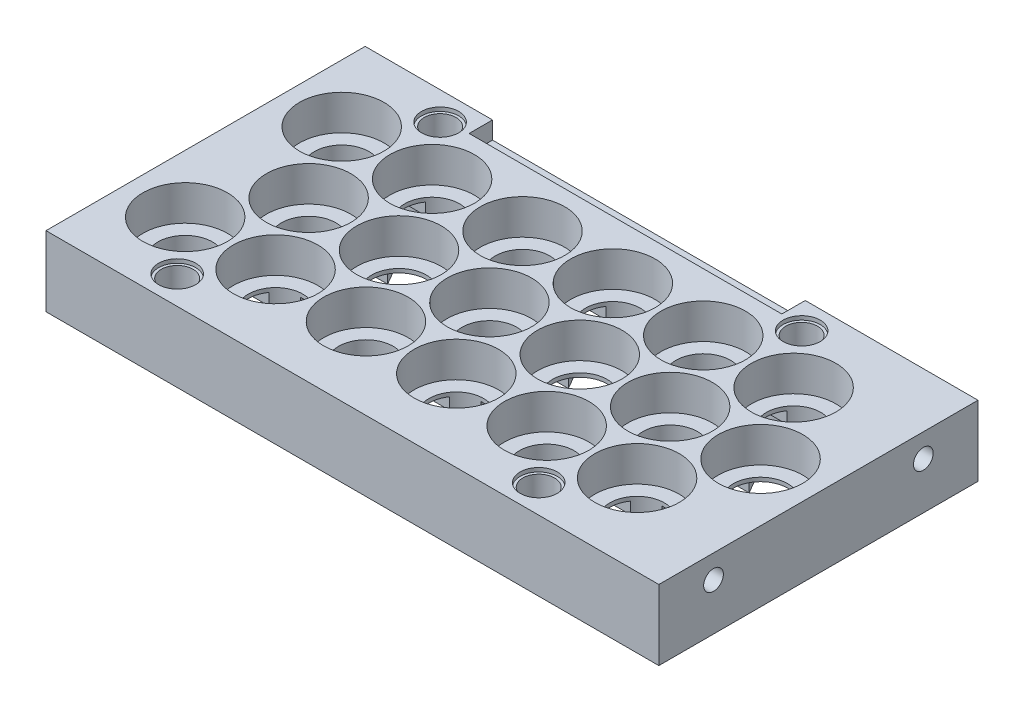
SolidWorks part; units mm, degrees
ref_plane "Front Plane" through (0, 0, 0) normal (0, 0, 1) x (1, 0, 0)
ref_plane "Top Plane" through (0, 0, 0) normal (0, 1, 0) x (1, 0, 0)
ref_plane "Right Plane" through (0, 0, 0) normal (1, 0, 0) x (0, 0, -1)
sketch "Sketch1" plane through (0, 0, 0) normal (0, 1, 0) x (1, 0, 0)
  line L0 (0, 0) -> (11.575, -20.0485) construction
  line L1 (11.575, -20.0485) -> (0, -40.097) construction
  line L2 (0, 0) -> (11.575, 0) construction
  line L3 (11.575, 0) -> (11.575, -20.0485) construction
  line L4 (11.575, -20.0485) -> (11.575, -40.097) construction
  line L5 (11.575, -40.097) -> (0, -40.097) construction
  line L6 (0, 0) -> (23.15, 0) construction
  line L7 (0, 0) -> (23.15, 0) construction
  line L8 (-14.825, -60.922) -> (142.15, -60.922)
  line L9 (-14.825, -60.922) -> (-14.825, 20.825)
  line L10 (-14.825, 20.825) -> (142.15, 20.825)
  line L11 (142.15, -60.922) -> (142.15, 20.825)
  circle A0 centre (0, 0) radius 10.825
  circle A1 centre (11.575, -20.0485) radius 10.825
  circle A2 centre (0, -40.097) radius 10.825
  circle A3 centre (23.15, 0) radius 10.825
  circle A4 centre (34.725, -20.0485) radius 10.825
  circle A5 centre (23.15, -40.097) radius 10.825
  circle A6 centre (46.3, 0) radius 10.825
  circle A7 centre (57.875, -20.0485) radius 10.825
  circle A8 centre (46.3, -40.097) radius 10.825
  circle A9 centre (69.45, 0) radius 10.825
  circle A10 centre (81.025, -20.0485) radius 10.825
  circle A11 centre (69.45, -40.097) radius 10.825
  circle A12 centre (92.6, 0) radius 10.825
  circle A13 centre (104.175, -20.0485) radius 10.825
  circle A14 centre (92.6, -40.097) radius 10.825
  circle A15 centre (115.75, 0) radius 10.825
  circle A16 centre (127.325, -20.0485) radius 10.825
  circle A17 centre (115.75, -40.097) radius 10.825
  circle A18 centre (0, 0) radius 7
  circle A19 centre (11.575, -20.0485) radius 7
  circle A20 centre (0, -40.097) radius 7
  circle A21 centre (23.15, 0) radius 7
  circle A22 centre (34.725, -20.0485) radius 7
  circle A23 centre (23.15, -40.097) radius 7
  circle A24 centre (46.3, 0) radius 7
  circle A25 centre (57.875, -20.0485) radius 7
  circle A26 centre (46.3, -40.097) radius 7
  circle A27 centre (69.45, 0) radius 7
  circle A28 centre (81.025, -20.0485) radius 7
  circle A29 centre (69.45, -40.097) radius 7
  circle A30 centre (92.6, 0) radius 7
  circle A31 centre (104.175, -20.0485) radius 7
  circle A32 centre (92.6, -40.097) radius 7
  circle A33 centre (115.75, 0) radius 7
  circle A34 centre (127.325, -20.0485) radius 7
  circle A35 centre (115.75, -40.097) radius 7
  dimension "D3" = 21.65
  dimension "D11" = 14
  dimension "D1" = 60
  dimension "D2" = 60
  dimension "D4" = 1.5
  dimension "D6" = 23.15
  dimension "D7" = 4
  dimension "D8" = 4
  dimension "D9" = 10
  dimension "D10" = 10
  dimension "D13" = 23.15
  dimension "D5" = 6
  dimension "D12" = 6
extrude "Boss-Extrude2" add sketch "Sketch1" along normal blind 11 and the other way blind 2 contours L8 L11 L10 L9 A17 A16 A15 A14 A13 A12 A11 A10 A9 A8 A7 A6 A5 A4 A3 A2 A1 A0 region at (-13.0551, 0, 20.0485)
extrude "Boss-Extrude3" add sketch "Sketch1<3>" along normal blind 2 and the other way up to surface (2 mm away) contours A0 A18 | A3 A21 | A6 A24 | A9 A27 | A12 A30 | A15 A33 | A1 A19 | A4 A22 | A7 A25 | A10 A28 | A13 A31 | A16 A34 | A17 A35 | A14 A32 | A11 A29 | A8 A26 | A5 A23 | A2 A20 region at (-10.5188, 0, 0) region at (1.0562, 0, 20.0485) region at (-10.5188, 0, 40.097) region at (12.6312, 0, 0) region at (24.2062, 0, 20.0485) region at (12.6312, 0, 40.097) region at (35.7812, 0, 0) region at (47.3562, 0, 20.0485) region at (35.7812, 0, 40.097) region at (58.9312, 0, 0) region at (70.5062, 0, 20.0485) region at (58.9312, 0, 40.097) region at (82.0812, 0, 0) region at (93.6562, 0, 20.0485) region at (82.0812, 0, 40.097) region at (105.2312, 0, 0) region at (116.8062, 0, 20.0485) region at (105.2312, 0, 40.097) other way up to face at (115.75, -2, 50.922)
sketch "Sketch1<3>" plane through (0, 0, 0) normal (0, 1, 0) x (1, 0, 0) same geometry as "Sketch1"
sketch "Sketch2" plane through (0, -2, 0) normal (0, -1, 0) x (1, 0, 0)
  line L0 (0, 40.097) -> (11.575, 20.0485) construction
  line L1 (3.4641, 42.097) -> (15.0391, 22.0485)
  line L2 (-3.4641, 38.097) -> (8.1109, 18.0485)
  line L3 (11.575, 20.0485) -> (0, 0) construction
  line L4 (15.0391, 18.0485) -> (3.4641, -2)
  line L5 (8.1109, 22.0485) -> (-3.4641, 2)
  line L6 (19.6859, 38.097) -> (31.2609, 18.0485)
  line L7 (26.6141, 42.097) -> (38.1891, 22.0485)
  line L8 (31.2609, 22.0485) -> (19.6859, 2)
  line L9 (38.1891, 18.0485) -> (26.6141, -2)
  line L10 (23.15, 40.097) -> (34.725, 20.0485) construction
  line L11 (34.725, 20.0485) -> (23.15, 0) construction
  line L12 (42.8359, 38.097) -> (54.4109, 18.0485)
  line L13 (49.7641, 42.097) -> (61.3391, 22.0485)
  line L14 (54.4109, 22.0485) -> (42.8359, 2)
  line L15 (61.3391, 18.0485) -> (49.7641, -2)
  line L16 (46.3, 40.097) -> (57.875, 20.0485) construction
  line L17 (57.875, 20.0485) -> (46.3, 0) construction
  line L18 (65.9859, 38.097) -> (77.5609, 18.0485)
  line L19 (72.9141, 42.097) -> (84.4891, 22.0485)
  line L20 (77.5609, 22.0485) -> (65.9859, 2)
  line L21 (84.4891, 18.0485) -> (72.9141, -2)
  line L22 (69.45, 40.097) -> (81.025, 20.0485) construction
  line L23 (81.025, 20.0485) -> (69.45, 0) construction
  line L24 (89.1359, 38.097) -> (100.7109, 18.0485)
  line L25 (96.0641, 42.097) -> (107.6391, 22.0485)
  line L26 (100.7109, 22.0485) -> (89.1359, 2)
  line L27 (107.6391, 18.0485) -> (96.0641, -2)
  line L28 (92.6, 40.097) -> (104.175, 20.0485) construction
  line L29 (104.175, 20.0485) -> (92.6, 0) construction
  line L30 (112.2859, 38.097) -> (123.8609, 18.0485)
  line L31 (119.2141, 42.097) -> (130.7891, 22.0485)
  line L32 (123.8609, 22.0485) -> (112.2859, 2)
  line L33 (130.7891, 18.0485) -> (119.2141, -2)
  line L34 (115.75, 40.097) -> (127.325, 20.0485) construction
  line L35 (127.325, 20.0485) -> (115.75, 0) construction
  line L36 (-3.4641, 38.097) -> (19.6859, 38.097) construction
  line L37 (0, 40.097) -> (115.75, 40.097) construction
  line L38 (0, 44.097) -> (115.75, 44.097)
  line L39 (0, 36.097) -> (115.75, 36.097)
  line L40 (11.575, 20.0485) -> (127.325, 20.0485) construction
  line L41 (11.575, 24.0485) -> (127.325, 24.0485)
  line L42 (11.575, 16.0485) -> (127.325, 16.0485)
  line L43 (0, 0) -> (115.75, 0) construction
  line L44 (0, 4) -> (115.75, 4)
  line L45 (0, -4) -> (115.75, -4)
  arc A0 (3.4641, 42.097) -> (-3.4641, 38.097) centre (0, 40.097) ccw
  arc A1 (8.1109, 18.0485) -> (15.0391, 22.0485) centre (11.575, 20.0485) ccw
  arc A2 (15.0391, 18.0485) -> (8.1109, 22.0485) centre (11.575, 20.0485) ccw
  arc A3 (-3.4641, 2) -> (3.4641, -2) centre (0, 0) ccw
  arc A4 (26.6141, 42.097) -> (19.6859, 38.097) centre (23.15, 40.097) ccw
  arc A5 (31.2609, 18.0485) -> (38.1891, 22.0485) centre (34.725, 20.0485) ccw
  arc A6 (38.1891, 18.0485) -> (31.2609, 22.0485) centre (34.725, 20.0485) ccw
  arc A7 (19.6859, 2) -> (26.6141, -2) centre (23.15, 0) ccw
  arc A8 (49.7641, 42.097) -> (42.8359, 38.097) centre (46.3, 40.097) ccw
  arc A9 (54.4109, 18.0485) -> (61.3391, 22.0485) centre (57.875, 20.0485) ccw
  arc A10 (61.3391, 18.0485) -> (54.4109, 22.0485) centre (57.875, 20.0485) ccw
  arc A11 (42.8359, 2) -> (49.7641, -2) centre (46.3, 0) ccw
  arc A12 (72.9141, 42.097) -> (65.9859, 38.097) centre (69.45, 40.097) ccw
  arc A13 (77.5609, 18.0485) -> (84.4891, 22.0485) centre (81.025, 20.0485) ccw
  arc A14 (84.4891, 18.0485) -> (77.5609, 22.0485) centre (81.025, 20.0485) ccw
  arc A15 (65.9859, 2) -> (72.9141, -2) centre (69.45, 0) ccw
  arc A16 (96.0641, 42.097) -> (89.1359, 38.097) centre (92.6, 40.097) ccw
  arc A17 (100.7109, 18.0485) -> (107.6391, 22.0485) centre (104.175, 20.0485) ccw
  arc A18 (107.6391, 18.0485) -> (100.7109, 22.0485) centre (104.175, 20.0485) ccw
  arc A19 (89.1359, 2) -> (96.0641, -2) centre (92.6, 0) ccw
  arc A20 (119.2141, 42.097) -> (112.2859, 38.097) centre (115.75, 40.097) ccw
  arc A21 (123.8609, 18.0485) -> (130.7891, 22.0485) centre (127.325, 20.0485) ccw
  arc A22 (130.7891, 18.0485) -> (123.8609, 22.0485) centre (127.325, 20.0485) ccw
  arc A23 (112.2859, 2) -> (119.2141, -2) centre (115.75, 0) ccw
  arc A24 (0, 44.097) -> (0, 36.097) centre (0, 40.097) ccw
  arc A25 (115.75, 36.097) -> (115.75, 44.097) centre (115.75, 40.097) ccw
  arc A26 (11.575, 24.0485) -> (11.575, 16.0485) centre (11.575, 20.0485) ccw
  arc A27 (127.325, 16.0485) -> (127.325, 24.0485) centre (127.325, 20.0485) ccw
  arc A28 (0, 4) -> (0, -4) centre (0, 0) ccw
  arc A29 (115.75, -4) -> (115.75, 4) centre (115.75, 0) ccw
  point P3 (5.7875, 30.0727)
  point P8 (5.7875, 10.0242)
  point P18 (28.9375, 30.0727)
  point P25 (28.9375, 10.0242)
  point P34 (52.0875, 30.0727)
  point P39 (52.0875, 10.0242)
  point P48 (75.2375, 30.0727)
  point P53 (75.2375, 10.0242)
  point P62 (98.3875, 30.0727)
  point P67 (98.3875, 10.0242)
  point P76 (121.5375, 30.0727)
  point P81 (121.5375, 10.0242)
  point P91 (57.875, 40.097)
  point P96 (69.45, 20.0485)
  point P103 (57.875, 0)
  circle M99 centre (0, 0) radius 7
  circle M100 centre (23.15, 0) radius 7
  circle M101 centre (46.3, 0) radius 7
  circle M102 centre (69.45, 0) radius 7
  circle M103 centre (92.6, 0) radius 7
  circle M104 centre (115.75, 0) radius 7
  circle M105 centre (11.575, 20.0485) radius 7
  circle M106 centre (34.725, 20.0485) radius 7
  circle M107 centre (57.875, 20.0485) radius 7
  circle M108 centre (81.025, 20.0485) radius 7
  circle M109 centre (104.175, 20.0485) radius 7
  circle M110 centre (127.325, 20.0485) radius 7
  circle M111 centre (115.75, 40.097) radius 7
  circle M112 centre (92.6, 40.097) radius 7
  circle M113 centre (69.45, 40.097) radius 7
  circle M114 centre (46.3, 40.097) radius 7
  circle M115 centre (23.15, 40.097) radius 7
  circle M116 centre (0, 40.097) radius 7
  dimension "D1" = 8
  dimension "D3" = 23.15
  dimension "D4" = 8
  dimension "D5" = 8
  dimension "D6" = 8
extrude "Cut-Extrude1" cut sketch "Sketch2" against normal blind 3 contours L1 L39 L38 M115 M116 | L6 L41 L7 L39 M106 M115 | L42 L8 L6 L41 M105 M106 | L45 L44 L4 M99 M100 | L44 L9 L42 L8 M100 M106 | L8 L42 M106 | L41 L6 M106 | L39 L1 M116 | L44 L4 M99 | L44 L9 M100 | L42 L20 L18 L41 M107 M108 | L45 L44 L15 M101 M102 | L13 L39 L38 M113 M114 | L18 L41 L19 L39 M108 M113 | L44 L21 L42 L20 M102 M108 | L45 L44 L27 M103 M104 | L42 L32 L30 L41 M109 M110 | L25 L39 L38 M111 M112 | L30 L41 L31 M110 M111 | L42 L32 L33 M104 M110 | L32 L42 M110 | L41 L30 M110 | L44 L27 M103 | L39 L25 M112 | L44 L21 M102 | L39 L19 M113 | L44 L15 M101 | L20 L42 M108 | L41 L18 M108 | L39 L13 M114 | L39 L7 M115 region at (11.6138, -2, 40.1242) region at (6.3461, -2, 36.4331) region at (23.0718, -2, 20.0485) region at (28.9375, -2, 30.0727) region at (28.3789, -2, 23.7124) region at (29.4961, -2, 36.4331) region at (57.9138, -2, 40.1242) region at (28.3789, -2, 16.3846) region at (28.9375, -2, 10.0242) region at (6.3461, -2, 3.6639) region at (11.6138, -2, -0.0272) region at (52.6461, -2, 36.4331) region at (29.4961, -2, 3.6639) region at (75.2375, -2, 30.0727) region at (75.7961, -2, 36.4331) region at (104.2138, -2, 40.1242) region at (74.6789, -2, 23.7124) region at (69.3718, -2, 20.0485) region at (57.9138, -2, -0.0272) region at (98.9461, -2, 36.4331) region at (74.6789, -2, 16.3846) region at (52.6461, -2, 3.6639) region at (121.5416, -2, 30.12) region at (75.2375, -2, 10.0242) region at (120.9789, -2, 23.7124) region at (115.6718, -2, 20.0485) region at (75.7961, -2, 3.6639) region at (104.2138, -2, -0.0272) region at (121.5416, -2, 9.977) region at (120.9789, -2, 16.3846) region at (98.9461, -2, 3.6639)
sketch "Sketch9" plane through (0, 11, 0) normal (0, 1, 0) x (1, 0, 0)
  line L0 (11.575, -60.922) -> (11.575, 20.825)
  line L1 (-14.825, 20.825) -> (142.15, 20.825) construction
  line L2 (104.175, 20.825) -> (104.175, -60.922)
  line L3 (-14.825, -60.922) -> (142.15, -60.922) construction
  circle A0 centre (11.575, 13.625) radius 4.0767
  circle A1 centre (11.575, -53.722) radius 4.0767
  circle A2 centre (104.175, -53.722) radius 4.0767
  circle A3 centre (104.175, 13.625) radius 4.0767
  point P0 (11.575, 13.625)
  point P7 (11.575, -20.0485)
  point P15 (104.175, -20.0485)
  point P20 (104.175, 13.625)
  point P21 (104.175, -53.722)
  point P22 (11.575, -53.722)
  dimension "D5" = 8.1534
  dimension "D1" = 7.2
  dimension "D4" = 7.2
extrude "Cut-Extrude3" cut sketch "Sketch9" against normal up to next contours A2 | A1 | A0 | A3
sketch "Sketch10" plane through (0, 11, 0) normal (0, 1, 0) x (1, 0, 0)
  circle A0 centre (11.575, 13.625) radius 4.7625
  circle A1 centre (104.175, 13.625) radius 4.7625
  circle A2 centre (104.175, -53.722) radius 4.7625
  circle A3 centre (11.575, -53.722) radius 4.7625
  dimension "D1" = 9.525
extrude "Cut-Extrude4" cut sketch "Sketch10" against normal blind 1
sketch "Sketch13" plane through (0, -2, 0) normal (0, -1, 0) x (1, 0, 0)
  line L0 (142.15, 60.922) -> (142.15, -20.825) construction
  line L5 (3.575, 53.722) -> (3.575, 60.922)
  line L8 (-14.825, 60.922) -> (142.15, 60.922) construction
  line L9 (3.575, 60.922) -> (19.575, 60.922)
  line L10 (19.575, 60.922) -> (19.575, 53.722)
  line L12 (57.875, 20.0485) -> (57.875, -20.825) construction
  line L13 (-14.825, -20.825) -> (142.15, -20.825) construction
  line L14 (11.575, 20.0485) -> (127.325, 20.0485) construction
  line L16 (96.175, 60.922) -> (96.175, 53.722)
  line L17 (112.175, 60.922) -> (96.175, 60.922)
  line L18 (112.175, 53.722) -> (112.175, 60.922)
  line L19 (-14.825, 60.922) -> (142.15, 60.922)
  line L20 (-14.825, 60.922) -> (-14.825, 53.922)
  line L21 (-14.825, 53.922) -> (142.15, 53.922)
  line L22 (142.15, 60.922) -> (142.15, 53.922)
  line L23 (142.15, -20.825) -> (142.15, -13.825)
  line L24 (-14.825, -13.825) -> (142.15, -13.825)
  line L25 (-14.825, -20.825) -> (-14.825, -13.825)
  line L26 (-14.825, -20.825) -> (142.15, -20.825)
  line L27 (112.175, -13.625) -> (112.175, -20.825)
  line L28 (112.175, -20.825) -> (96.175, -20.825)
  line L29 (96.175, -20.825) -> (96.175, -13.625)
  line L32 (19.575, -20.825) -> (19.575, -13.625)
  line L33 (3.575, -20.825) -> (19.575, -20.825)
  line L34 (3.575, -13.625) -> (3.575, -20.825)
  line L36 (-14.825, 53.922) -> (-9.825, 53.922)
  line L37 (-14.825, 53.922) -> (-14.825, -13.825)
  line L38 (-14.825, -13.825) -> (-9.825, -13.825)
  line L39 (-9.825, 53.922) -> (-9.825, -13.825)
  line L40 (142.15, 53.922) -> (137.15, 53.922)
  line L41 (142.15, 53.922) -> (142.15, -13.825)
  line L42 (142.15, -13.825) -> (137.15, -13.825)
  line L43 (137.15, 53.922) -> (137.15, -13.825)
  circle A4 centre (11.575, 53.722) radius 4.0767
  circle A5 centre (11.575, 53.722) radius 8
  circle A6 centre (104.175, 53.722) radius 8
  circle A7 centre (104.175, 53.722) radius 4.0767
  circle A8 centre (104.175, -13.625) radius 4.0767
  circle A9 centre (104.175, -13.625) radius 8
  circle A10 centre (11.575, -13.625) radius 8
  circle A11 centre (11.575, -13.625) radius 4.0767
  circle A12 centre (11.575, 53.722) radius 4.0767 construction
  dimension "D2" = 16
  dimension "D3" = 7
  dimension "D1" = 5
  dimension "D4" = 5
extrude "Boss-Extrude7" add sketch "Sketch13" along normal blind 5 contours L21 L5 | A5 L5 L21 | A5 L21 L10 | L10 L21 L16 | L21 A5 L19 A4 | A5 L21 A4 | L21 A6 L16 | L21 A7 A6 L19 | L21 A7 A6 | A6 L21 L18 | L18 L21 | A9 L24 L29 L26 | L28 A9 L24 A8 | A9 L26 L27 L24 | L24 L27 L26 | L32 L26 L29 L24 | L24 A9 A8 | L34 L24 | L26 A10 L24 L34 | L24 A11 A10 | L24 A11 A10 L33 | L24 A10 L26 L32 | L39 L21 L37 L24 | L21 L43 L24 L41 region at (3.7554, -2, 53.8197) region at (-5.625, -2, 57.422) region at (4.8234, -2, 59.2386) region at (4.9969, -2, 57.9605) region at (-12.325, -2, 20.0485) region at (18.3266, -2, 59.2386) region at (57.875, -2, 57.422) region at (-5.625, -2, -17.325) region at (97.4234, -2, 59.2386) region at (4.8234, -2, -19.1416) region at (96.3554, -2, 53.8197) region at (97.5969, -2, 57.9605) region at (3.7554, -2, -13.7228) region at (5.5404, -2, -13.9996) region at (110.9266, -2, 59.2386) region at (127.1625, -2, 57.422) region at (18.3266, -2, -19.1416) region at (57.875, -2, -17.325) region at (139.65, -2, 20.0485) region at (97.4234, -2, -19.1416) region at (127.1625, -2, -17.325) region at (96.3554, -2, -13.7228) region at (98.1404, -2, -13.9996) region at (110.9266, -2, -19.1416)
sketch "Sketch18" plane through (0, 0, -20.825) normal (0, 0, -1) x (-1, 0, 0)
  line L1 (-97.9, 11) -> (-17.8, 11)
  line L2 (-97.9, 11) -> (-17.8, 11)
  line L3 (-97.9, 11) -> (-97.9, 6.525)
  line L4 (-17.8, 11) -> (-17.8, 6.525)
  line L5 (-97.9, 6.525) -> (-17.8, 6.525)
  line L6 (-104.15, 11) -> (-11.55, 11)
  line L7 (14.825, 11) -> (-142.15, 11) construction
  point P7 (-57.85, 11)
  point P10 (-57.85, 11)
  line M8 (14.825, 11) -> (-142.15, 11)
  dimension "D1" = 80.1
  dimension "D2" = 4.475
  dimension "D3" = 92.6
  dimension "D4" = 38
extrude "Cut-Extrude6" cut sketch "Sketch18" against normal blind 6 contours L3 L5 L4 M8 region at (57.85, 8.7625, -20.825)
sketch "Sketch19" plane through (0, 0, -20.825) normal (0, 0, -1) x (-1, 0, 0)
  line L0 (-85.9, 6.525) -> (-29.8, 6.525)
  line L1 (-85.9, 6.525) -> (-85.9, -0.2375)
  line L2 (-29.8, 6.525) -> (-29.8, -0.2375)
  line L3 (-85.9, -0.2375) -> (-29.8, -0.2375)
  line L4 (-97.9, 6.525) -> (-17.8, 6.525) construction
  line L5 (-97.9, 6.525) -> (-17.8, 6.525) construction
  line L6 (-85.9, 6.525) -> (-97.9, 6.525) construction
  line L7 (-29.8, 6.525) -> (-17.8, 6.525) construction
  line L8 (-57.85, 6.525) -> (-57.85, -7)
  line L9 (14.825, -7) -> (-142.15, -7) construction
  circle A0 centre (-85.9, -0.2375) radius 1.9431
  circle A1 centre (-29.8, -0.2375) radius 1.9431
  point P17 (-57.85, -0.2375)
  dimension "D2" = 3.8862
  dimension "D1" = 12
extrude "Cut-Extrude7" cut sketch "Sketch19" against normal blind 5 contours L1 A0 L3 | L3 A0 L1 | L3 A1 L2 | L2 A1 L3 region at (85.0753, 0.5872, -20.825) region at (86.1749, -0.5124, -20.825) region at (29.5251, -0.5124, -20.825) region at (30.6247, 0.5872, -20.825)
sketch "Sketch20" plane through (142.15, 0, 0) normal (1, 0, 0) x (0, 0, -1)
  line L0 (-46.922, 5) -> (-60.922, 5)
  line L1 (6.825, 5) -> (20.825, 5)
  line L2 (-46.922, 5) -> (-46.922, 11)
  line L3 (6.825, 5) -> (6.825, 11)
  line L4 (-60.922, 11) -> (20.825, 11) construction
  line L5 (20.825, 11) -> (20.825, -7) construction
  line L6 (-60.922, 11) -> (-60.922, -7) construction
  circle A0 centre (-46.922, 5) radius 2.5273
  circle A1 centre (6.825, 5) radius 2.5273
  dimension "D1" = 5.0546
  dimension "D2" = 14
  dimension "D3" = 6
extrude "Cut-Extrude8" cut sketch "Sketch20" against normal blind 10 contours L0 A0 L2 | L2 A0 L0 | A1 region at (142.15, 4.6425, 46.5644) region at (142.15, 6.0726, 47.9946)
sketch "Sketch21" plane through (0, -2, 0) normal (0, -1, 0) x (1, 0, 0)
  line L0 (57.875, 44.097) -> (57.875, 53.922) construction
  line L1 (52.0446, 44.097) -> (63.7054, 44.097) construction
  line L2 (19.5725, 53.922) -> (96.1775, 53.922) construction
  line L3 (121.4946, 44.097) -> (137.15, 44.097) construction
  line L4 (137.15, 53.922) -> (137.15, -13.825) construction
  line L5 (57.875, 20.0485) -> (-2.625, 20.0485) construction
  line L6 (4.575, 20.0485) -> (-9.825, 20.0485) construction
  line L7 (-9.825, 53.922) -> (-9.825, -13.825) construction
  line L8 (121.4946, -4) -> (137.15, -4) construction
  line L9 (57.875, -4) -> (57.875, -13.825) construction
  circle A0 centre (57.875, 49.0095) radius 1.9431
  circle A1 centre (129.3223, 44.097) radius 1.9431
  arc A2 (122.0864, 37.122) -> (110.0054, 44.097) centre (115.75, 40.097) ccw construction
  circle A3 centre (-2.625, 20.0485) radius 1.9431
  arc A4 (17.3196, 24.0485) -> (17.3196, 16.0485) centre (11.575, 20.0485) ccw construction
  circle A5 centre (129.3223, -4) radius 1.9431
  circle A6 centre (57.875, -8.9125) radius 1.9431
  point P21 (0, 0)
  point P22 (-2.625, 20.0485)
  dimension "D1" = 3.8862
extrude "Cut-Extrude9" cut sketch "Sketch21" against normal blind 3.81
equation "\"hole_diameter\"= 21.65"
equation "\"D3@Sketch1\"=\"hole_diameter\""
equation "\"cell_spacing\"= 1.5"
equation "\"D4@Sketch1\"=\"cell_spacing\""
equation "\"D6@Sketch1\"=\"hole_diameter\"+\"cell_spacing\""
equation "\"len_spacing\"= 4"
equation "\"D7@Sketch1\"=\"len_spacing\""
equation "\"D8@Sketch1\"=\"len_spacing\""
equation "\"wid_spacing\"= 10"
equation "\"D9@Sketch1\"=\"wid_spacing\""
equation "\"D10@Sketch1\"=\"wid_spacing\""
equation "\"nipple\"= 14"
equation "\"D11@Sketch1\"=\"nipple\""
equation "\"D13@Sketch1\"=\"hole_diameter\"+\"cell_spacing\""
equation "\"channel\"= 8"
equation "\"D1@Sketch2\"=\"channel\""
equation "\"D3@Sketch2\"=\"hole_diameter\"+\"cell_spacing\""
equation "\"D4@Sketch2\"=\"channel\""
equation "\"D5@Sketch2\"=\"channel\""
equation "\"D6@Sketch2\"=\"channel\""
equation "\"lip\"= 7"
equation "\"lip_height\"= 1"
equation "\"outer_fillet\"=6"
equation "\"insert_placement\"= 7.2"
equation "\"D4@Sketch9\"=\"insert_placement\""
equation "\"D1@Sketch9\"=\"insert_placement\""
equation "\"heat_insert_diameter\"=8.1534"
equation "\"D5@Sketch9\"=\"heat_insert_diameter\""
equation "\"heat_insert_lip_diameter\"=9.525"
equation "\"D1@Sketch10\"=\"heat_insert_lip_diameter\""
equation "\"bolt_head_diameter\"=13"
equation "\"D2@Sketch13\"=\"bolt_head_diameter\"+3"
equation "\"D3@Sketch13\"=\"lip\""
equation "\"small_heat_insert\"= .153in"
equation "\"bdm_cut_depth\"=6"
equation "\"D1@Cut-Extrude6\"=\"bdm_cut_depth\""
equation "\"D2@Sketch19\"=\"small_heat_insert\""
equation "\"heat_insert_depth\"=3.81"
equation "\"D1@Sketch21\"=\"small_heat_insert\""
equation "\"heat_insert_space\"=6"
equation "\"heat_insert\"=5.5"
